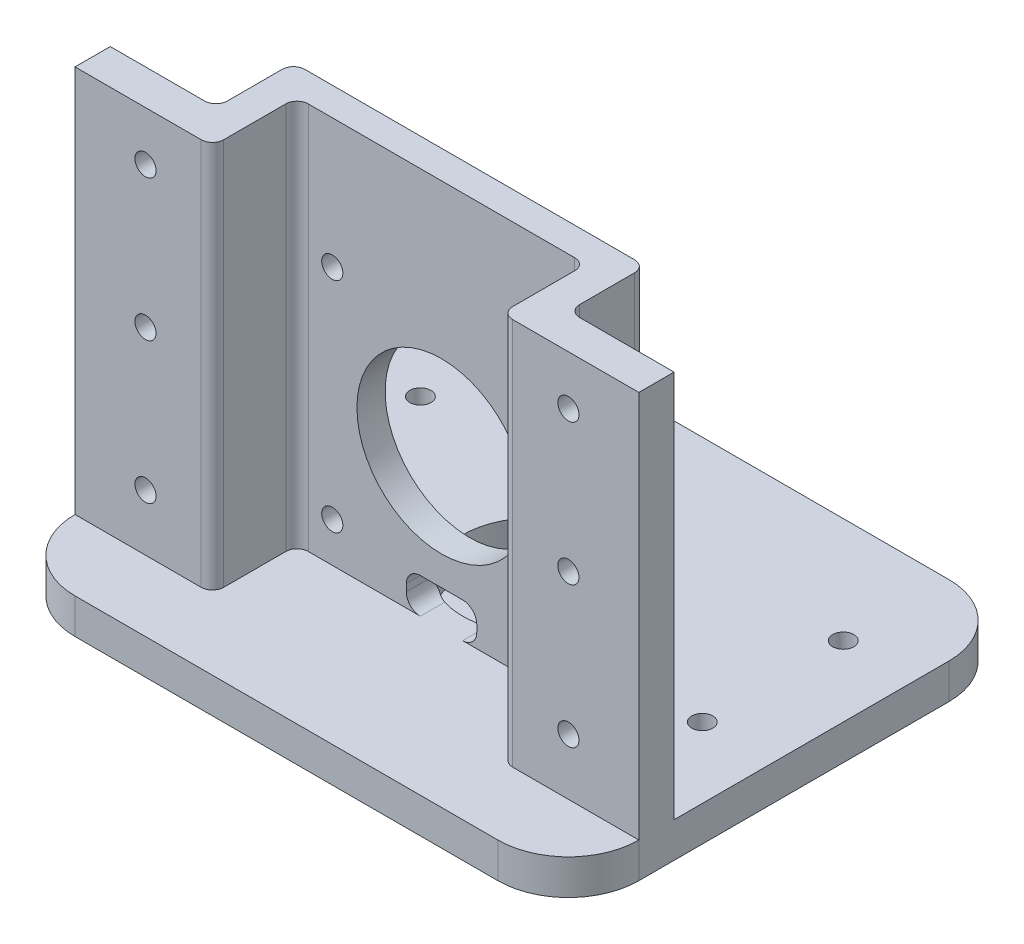
SolidWorks part; units mm, degrees
material "聚脂树脂"
ref_plane "前视基准面" through (0, 0, 0) normal (0, 0, 1) x (1, 0, 0)
ref_plane "上视基准面" through (0, 0, 0) normal (0, 1, 0) x (1, 0, 0)
ref_plane "右视基准面" through (0, 0, 0) normal (1, 0, 0) x (0, 0, -1)
other "Configuration Table"
sketch "草图1" plane through (0, 0, 0) normal (0, 1, 0) x (1, 0, 0)
  line L0 (0, 0) -> (58.6016, 0) construction
  line L1 (-40, -35) -> (40, -35)
  line L2 (-40, -35) -> (-40, 35)
  line L3 (-40, 35) -> (40, 35)
  line L4 (40, -35) -> (40, 35)
  line L5 (-40, -35) -> (40, 35) construction
  line L6 (-40, 35) -> (40, -35) construction
  line L7 (0, 0) -> (0, 47.0411) construction
  line L8 (0, 5) -> (44.8156, 5) construction
  circle A0 centre (0, 0) radius 10
  point P0 (0, 0)
  dimension "D3" = 20
  dimension "D1" = 70
  dimension "D2" = 80
  dimension "D6" = 5
extrude "凸台-拉伸1" add sketch "草图1" along normal blind 5
sketch "草图2" plane through (0, 5, 0) normal (0, 1, 0) x (1, 0, 0)
  line L0 (0, 0) -> (55.3583, 0) construction
  line L1 (0, 0) -> (0, 46.1954) construction
  line L2 (0, 0) -> (0, -38.3673) construction
  line L3 (-25, -9) -> (25, -9)
  line L4 (25, -9) -> (25, -20)
  line L5 (25, -20) -> (40, -20)
  line L6 (40, -20) -> (40, -25)
  line L7 (40, -25) -> (20.5, -25)
  line L8 (20.5, -25) -> (20.5, -13)
  line L9 (20.5, -13) -> (-20.5, -13)
  line L10 (-20.5, -25) -> (-20.5, -13)
  line L11 (-40, -25) -> (-20.5, -25)
  line L12 (-40, -20) -> (-40, -25)
  line L13 (-25, -20) -> (-40, -20)
  line L14 (-25, -9) -> (-25, -20)
  point P14 (0, -13)
  point P19 (0, -9)
  dimension "D1" = 25
  dimension "D2" = 11
  dimension "D3" = 20.5
  dimension "D4" = 12
  dimension "D5" = 19.5
  dimension "D6" = 9
  dimension "D7" = 4
extrude "凸台-拉伸2" add sketch "草图2" along normal blind 55
sketch "草图3" plane through (0, 0, 13) normal (0, 0, 1) x (1, 0, 0)
  line L0 (0, 0) -> (0, 69.1059) construction
  line L1 (0, 0) -> (57.4199, 0) construction
  line L2 (0, 5) -> (40.8093, 5) construction
  line L3 (-40, 5) -> (40, 5) construction
  line L4 (0, 26.15) -> (45.791, 26.15) construction
  line L5 (-30, 13) -> (-30, 61.5047) construction
  line L6 (-40, 5) -> (-20.5, 5) construction
  circle A0 centre (0, 26.15) radius 12
  circle A1 centre (15.5, 41.65) radius 1.5
  circle A2 centre (15.5, 10.65) radius 1.5
  circle A3 centre (-15.5, 10.65) radius 1.5
  circle A4 centre (-15.5, 41.65) radius 1.5
  circle A5 centre (-30, 13) radius 1.5
  circle A6 centre (-30, 33) radius 1.5
  circle A7 centre (-30, 53) radius 1.5
  circle A8 centre (30, 53) radius 1.5
  circle A9 centre (30, 33) radius 1.5
  circle A10 centre (30, 13) radius 1.5
  dimension "D2" = 24
  dimension "D3" = 3
  dimension "D4" = 31
  dimension "D5" = 31
  dimension "D6" = 3
  dimension "D7" = 3
  dimension "D8" = 3
  dimension "D9" = 20
  dimension "D10" = 20
  dimension "D11" = 8
  dimension "D1" = 21.15
  dimension "D12" = 30
extrude "切除-拉伸1" cut sketch "草图3" along normal blind 60 and the other way blind 60
fillet "圆角3" radius 1.6 8 edges at (20.5, 32.5, 25) (20.5, 32.5, 13) (-20.5, 32.5, 25) (-20.5, 32.5, 13) (25, 32.5, 20) (25, 32.5, 9) (-25, 32.5, 9) (-25, 32.5, 20)
sketch "草图4" plane through (0, 5, 0) normal (0, 1, 0) x (1, 0, 0)
  line L0 (0, 0) -> (50.2662, 0) construction
  line L1 (0, 0) -> (0, 50.3436) construction
  line L2 (30, -23.9509) -> (30, 23.9509) construction
  circle A0 centre (30, 14) radius 1.5
  circle A1 centre (30, -6) radius 1.5
  circle A2 centre (-30, -6) radius 1.5
  circle A3 centre (-30, 14) radius 1.5
  point P11 (30, 0)
  point P17 (-30, 0)
  dimension "D1" = 3
  dimension "D2" = 3
  dimension "D3" = 20
  dimension "D4" = 14
  dimension "D5" = 30
extrude "切除-拉伸2" cut sketch "草图4" against normal blind 10
sketch "草图5" plane through (0, 5, 0) normal (0, 1, 0) x (1, 0, 0)
  line L0 (-40, 29) -> (-40, 35)
  line L1 (-40, 35) -> (-40, -20) construction
  line L2 (-40, 35) -> (40, 35)
  line L3 (40, 35) -> (40, 29)
  line L4 (40, -20) -> (40, 35) construction
  line L5 (40, 29) -> (-40, 29)
  dimension "D1" = 6
extrude "切除-拉伸3" cut sketch "草图5" against normal blind 10
fillet "圆角4" radius 10 4 edges at (40, 2.5, -29) (-40, 2.5, -29) (40, 2.5, 35) (-40, 2.5, 35)
sketch "草图6" plane through (0, 0, 13) normal (0, 0, 1) x (1, 0, 0)
  line L0 (0, 5) -> (5, 5)
  line L1 (-18.9, 5) -> (18.9, 5) construction
  line L2 (5, 5) -> (5, 10)
  line L3 (5, 10) -> (-5, 10)
  line L4 (-5, 10) -> (-5, 5)
  line L5 (-30, 5) -> (30, 5) construction
  line L6 (-5, 5) -> (0, 5)
  dimension "D1" = 5
  dimension "D2" = 5
  dimension "D3" = 5
extrude "切除-拉伸4" cut sketch "草图6" against normal blind 10
fillet "圆角5" radius 2 4 edges at (5, 5, 11) (5, 10, 11) (-5, 5, 11) (-5, 10, 11)
sketch "草图8" plane through (0, 0, 0) normal (0, -1, 0) x (1, 0, 0)
  line L0 (0, 0) -> (46.425, 0) construction
  line L1 (-25, -22.5) -> (25, -22.5)
  line L2 (-25, -22.5) -> (-25, 22.5)
  line L3 (-25, 22.5) -> (25, 22.5)
  line L4 (25, -22.5) -> (25, 22.5)
  line L5 (-25, -22.5) -> (25, 22.5) construction
  line L6 (-25, 22.5) -> (25, -22.5) construction
  line L7 (0, 0) -> (0, 48.1856) construction
  circle A0 centre (0, 0) radius 3.5
  circle A1 centre (0, 7) radius 1.5
  circle A2 centre (7, 0) radius 1.5
  circle A3 centre (-7, 0) radius 1.5
  circle A4 centre (0, -7) radius 1.5
  point P0 (0, 0)
  dimension "D3" = 7
  dimension "D4" = 3
  dimension "D5" = 3
  dimension "D6" = 7
  dimension "D1" = 50
  dimension "D2" = 45
  dimension "D7" = 7
extrude "凸台-拉伸3" add sketch "草图8" along normal blind 3
fillet "圆角6" radius 10 4 edges at (25, -1.5, -22.5) (-25, -1.5, -22.5) (25, -1.5, 22.5) (-25, -1.5, 22.5)
sketch "草图10" plane through (0, -3, 0) normal (0, -1, 0) x (1, 0, 0)
  circle A0 centre (0, 0) radius 12
  circle A1 centre (0, -7) radius 1.5 construction
  circle A2 centre (-7, 0) radius 1.5 construction
  circle A3 centre (7, 0) radius 1.5 construction
  circle A4 centre (0, 0) radius 3.5 construction
  circle A5 centre (0, 7) radius 1.5 construction
  circle A6 centre (0, -7) radius 1.5
  circle A7 centre (-7, 0) radius 1.5
  circle A8 centre (7, 0) radius 1.5
  circle A9 centre (0, 0) radius 3.5
  circle A10 centre (0, 7) radius 1.5
  dimension "D1" = 24
extrude "凸台-拉伸4" add sketch "草图10" along normal blind 5
sketch "草图12" plane through (0, -8, 0) normal (0, -1, 0) x (1, 0, 0)
  circle A0 centre (0, 0) radius 10.5
  circle A1 centre (0, 0) radius 12
  dimension "D1" = 21
  dimension "D2" = 24
extrude "凸台-拉伸5" add sketch "草图12" along normal blind 4
sketch "草图13" plane through (0, -3, 0) normal (0, -1, 0) x (1, 0, 0)
  circle A0 centre (0, 0) radius 21
  circle A1 centre (0, 0) radius 12
  dimension "D1" = 42
  dimension "D2" = 24
extrude "凸台-拉伸6" add sketch "草图13" along normal blind 2
